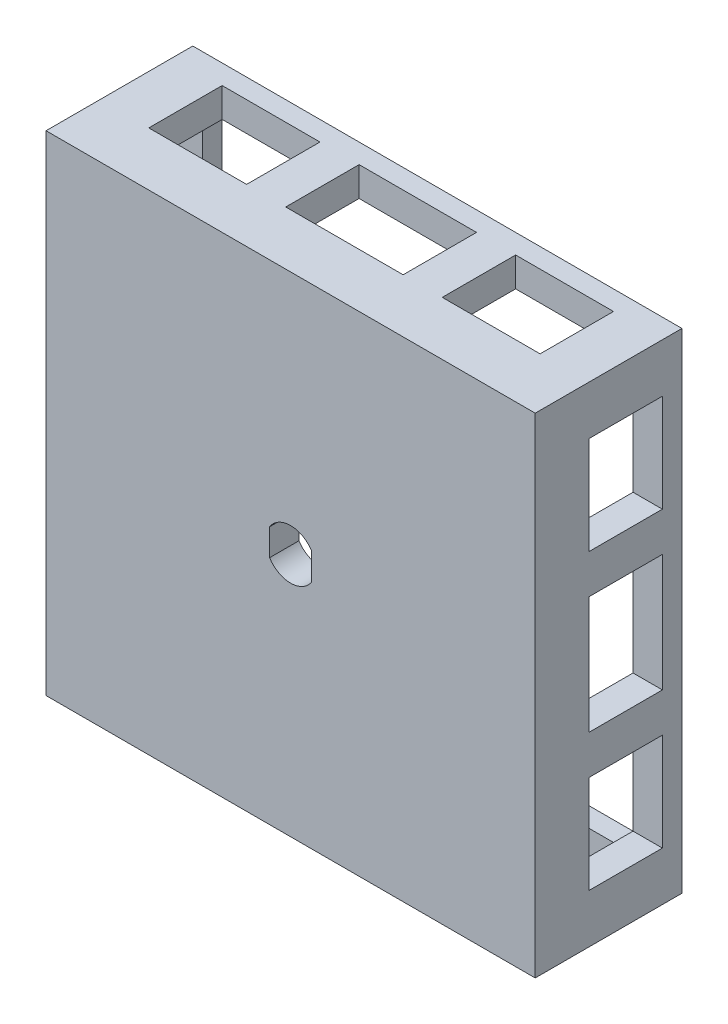
SolidWorks part; units mm, degrees
ref_plane "Front Plane" through (0, 0, 0) normal (0, 0, 1) x (1, 0, 0)
ref_plane "Top Plane" through (0, 0, 0) normal (0, 1, 0) x (1, 0, 0)
ref_plane "Right Plane" through (0, 0, 0) normal (1, 0, 0) x (0, 0, -1)
sketch "Sketch1" plane through (0, 0, 0) normal (0, 0, 1) x (1, 0, 0)
  line L1 (-25, -25) -> (25, -25)
  line L2 (-25, -25) -> (-25, 25)
  line L3 (-25, 25) -> (25, 25)
  line L4 (25, -25) -> (25, 25)
  line L5 (-25, -25) -> (25, 25) construction
  line L6 (-25, 25) -> (25, -25) construction
  point P0 (0, 0)
  dimension "D1" = 50
  dimension "D2" = 50
extrude "Boss-Extrude1" add sketch "Sketch1" along normal blind 15
shell "Shell1" thickness 3 removed face at (0, 0, 0)
sketch "Sketch2" plane through (0, 0, 0) normal (0, 0, -1) x (-1, 0, 0)
  line L0 (0, 2.55) -> (0, -2.55) construction
  line L1 (-2.15, 1.3711) -> (-2.15, -1.3711)
  line L2 (2.15, 1.3711) -> (2.15, -1.3711)
  arc A0 (-2.15, -1.3711) -> (2.15, -1.3711) centre (0, 0) ccw
  arc A1 (-2.15, 1.3711) -> (-2.15, -1.3711) centre (0, 0) ccw construction
  arc A2 (2.15, 1.3711) -> (-2.15, 1.3711) centre (0, 0) ccw
  arc A3 (2.15, -1.3711) -> (2.15, 1.3711) centre (0, 0) ccw construction
  dimension "D1" = 5.1
  dimension "D2" = 2.15
extrude "Cut-Extrude1" cut sketch "Sketch2" against normal through all both and the other way through all
sketch "Sketch4" plane through (0, 0, 0) normal (0, 0, -1) x (-1, 0, 0)
  line L0 (-17.5, 17.5) -> (-17.5, 27.9484)
  line L1 (26.9415, -17.5) -> (17.5, -17.5)
  line L2 (26.9415, -17.5) -> (26.9415, 17.5)
  line L3 (26.9415, 17.5) -> (17.5, 17.5)
  line L4 (-26.9415, -17.5) -> (-26.9415, 17.5)
  line L5 (26.9415, -17.5) -> (-26.9415, 17.5) construction
  line L6 (26.9415, 17.5) -> (-26.9415, -17.5) construction
  line L7 (17.5, -27.9484) -> (-17.5, -27.9484)
  line L8 (17.5, -27.9484) -> (17.5, -17.5)
  line L9 (17.5, 27.9484) -> (-17.5, 27.9484)
  line L10 (-17.5, -27.9484) -> (-17.5, -17.5)
  line L11 (17.5, -27.9484) -> (-17.5, 27.9484) construction
  line L12 (17.5, 27.9484) -> (-17.5, -27.9484) construction
  line L13 (-17.5, 11.3672) -> (-17.5, 17.5) construction
  line L14 (-17.5, -11.3672) -> (-17.5, 11.3672) construction
  line L15 (-17.5, -17.5) -> (-17.5, -11.3672) construction
  line L16 (-17.5, -17.5) -> (-26.9415, -17.5)
  line L17 (-10.9577, -17.5) -> (-17.5, -17.5) construction
  line L18 (10.9577, -17.5) -> (-10.9577, -17.5) construction
  line L19 (17.5, -17.5) -> (10.9577, -17.5) construction
  line L20 (17.5, 17.5) -> (17.5, 27.9484)
  line L21 (17.5, -17.5) -> (17.5, -11.3672) construction
  line L22 (17.5, -11.3672) -> (17.5, 11.3672) construction
  line L23 (17.5, 11.3672) -> (17.5, 17.5) construction
  line L24 (-17.5, 17.5) -> (-26.9415, 17.5)
  line L25 (17.5, 17.5) -> (10.9577, 17.5) construction
  line L26 (10.9577, 17.5) -> (-10.9577, 17.5) construction
  line L27 (-10.9577, 17.5) -> (-17.5, 17.5) construction
  point P0 (0, 0)
  point P6 (0, 0)
  dimension "D1" = 35
  dimension "D2" = 35
sketch "Sketch5" plane through (-25, 0, 0) normal (-1, 0, 0) x (0, 0, 1)
  line L8 (7.5, 25) -> (7.5, -25) construction
  line L13 (15, 25) -> (0, 25) construction
  line L14 (15, -25) -> (0, -25) construction
  line L19 (0, 0) -> (15, 0) construction
  line L20 (0, -11.3672) -> (0, 11.3672) construction
  line L25 (15, 25) -> (15, -25) construction
  line L28 (2, 10) -> (9.5, 10)
  line L29 (2, 10) -> (2, 20)
  line L30 (2, 20) -> (9.5, 20)
  line L31 (9.5, 10) -> (9.5, 20)
  line L32 (2, 10) -> (9.5, 20) construction
  line L33 (2, 20) -> (9.5, 10) construction
  line L34 (2, -6) -> (9.5, -6)
  line L35 (2, -6) -> (2, 6)
  line L36 (2, 6) -> (9.5, 6)
  line L37 (9.5, -6) -> (9.5, 6)
  line L38 (2, -6) -> (9.5, 6) construction
  line L39 (2, 6) -> (9.5, -6) construction
  line L40 (2, -20) -> (9.5, -20)
  line L41 (2, -20) -> (2, -10)
  line L42 (2, -10) -> (9.5, -10)
  line L43 (9.5, -20) -> (9.5, -10)
  line L44 (2, -20) -> (9.5, -10) construction
  line L45 (2, -10) -> (9.5, -20) construction
  line L46 (12, 22) -> (12, -22) construction
  point P14 (5.75, 15)
  point P19 (5.75, 0)
  point P24 (5.75, -15)
  dimension "D1" = 2.5
  dimension "D2" = 10
  dimension "D3" = 12
  dimension "D4" = 10
  dimension "D5" = 2.5
  dimension "D6" = 2.5
  dimension "D7" = 7.5
  dimension "D8" = 7.5
  dimension "D9" = 7.5
  dimension "D10" = 10
  dimension "D11" = 10
extrude "Cut-Extrude2" cut sketch "Sketch5" against normal through all both and the other way through all
sketch "Sketch6" plane through (0, -25, 0) normal (0, -1, 0) x (1, 0, 0)
  line L0 (-25, 7.5) -> (25, 7.5) construction
  line L1 (-25, 15) -> (-25, 0) construction
  line L2 (25, 15) -> (25, 0) construction
  line L3 (0, 0) -> (0, 15) construction
  line L4 (-10.9577, 0) -> (10.9577, 0) construction
  line L5 (-25, 15) -> (25, 15) construction
  line L6 (-22, 12) -> (22, 12) construction
  line L7 (-6, 2) -> (6, 2)
  line L8 (-6, 2) -> (-6, 9.5)
  line L9 (-6, 9.5) -> (6, 9.5)
  line L10 (6, 2) -> (6, 9.5)
  line L11 (-6, 2) -> (6, 9.5) construction
  line L12 (-6, 9.5) -> (6, 2) construction
  line L13 (10, 9.5) -> (20, 9.5)
  line L14 (10, 9.5) -> (10, 2)
  line L15 (10, 2) -> (20, 2)
  line L16 (20, 9.5) -> (20, 2)
  line L17 (10, 9.5) -> (20, 2) construction
  line L18 (10, 2) -> (20, 9.5) construction
  line L19 (-20, 9.5) -> (-10, 9.5)
  line L20 (-20, 9.5) -> (-20, 2)
  line L21 (-20, 2) -> (-10, 2)
  line L22 (-10, 9.5) -> (-10, 2)
  line L23 (-20, 9.5) -> (-10, 2) construction
  line L24 (-20, 2) -> (-10, 9.5) construction
  point P12 (0, 5.75)
  point P17 (15, 5.75)
  point P22 (-15, 5.75)
  dimension "D1" = 10
  dimension "D2" = 12
  dimension "D3" = 10
  dimension "D4" = 10
  dimension "D5" = 10
  dimension "D6" = 2.5
  dimension "D7" = 2.5
  dimension "D8" = 2.5
  dimension "D9" = 7.5
  dimension "D10" = 7.5
  dimension "D11" = 7.5
extrude "Cut-Extrude3" cut sketch "Sketch6" against normal through all both and the other way through all
